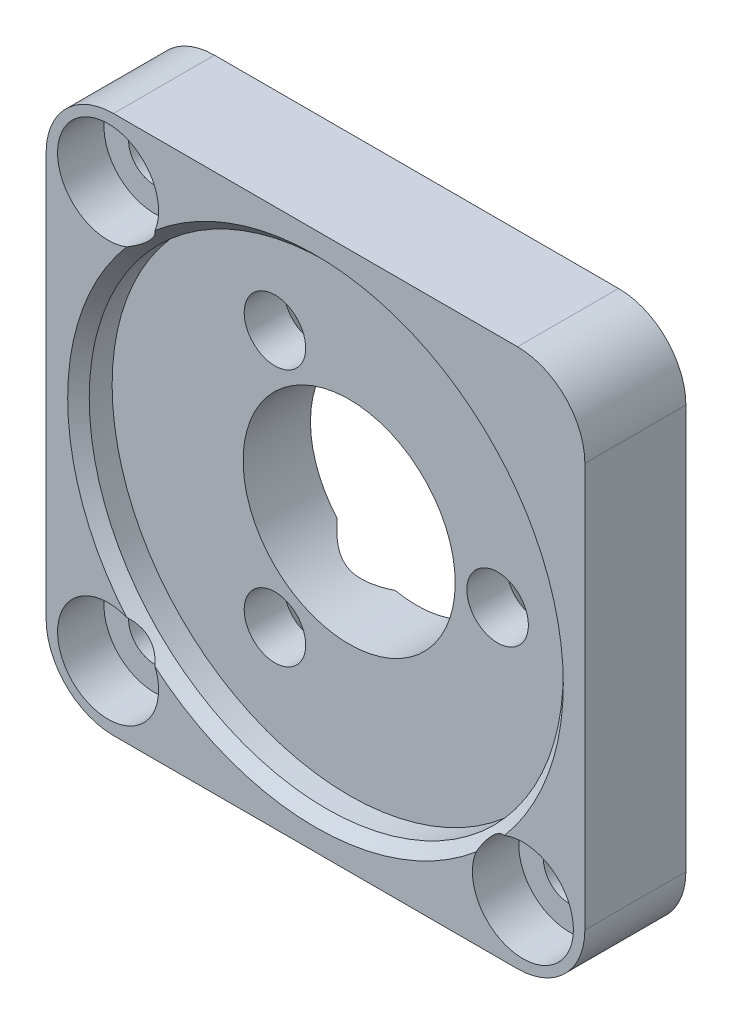
SolidWorks part; units mm, degrees
material "6063-T6"
ref_plane "Front Plane" through (0, 0, 0) normal (0, 0, 1) x (1, 0, 0)
ref_plane "Top Plane" through (0, 0, 0) normal (0, 1, 0) x (1, 0, 0)
ref_plane "Right Plane" through (0, 0, 0) normal (1, 0, 0) x (0, 0, -1)
sketch "Sketch1" plane through (0, 0, 0) normal (0, 0, 1) x (1, 0, 0)
  line L1 (-12.7, -12.7) -> (12.7, -12.7)
  line L2 (-12.7, -12.7) -> (-12.7, 12.7)
  line L3 (-12.7, 12.7) -> (12.7, 12.7)
  line L4 (12.7, -12.7) -> (12.7, 12.7)
  line L5 (-12.7, -12.7) -> (12.7, 12.7)
  line L6 (-12.7, 12.7) -> (12.7, -12.7)
  circle A0 centre (0, 0) radius 11.1125 construction
  dimension "D1" = 22.225
  dimension "D2" = 25.4
  dimension "D3" = 25.4
extrude "Boss-Extrude2" add sketch "Sketch1" along normal blind 4.7625 contours L3 L6 L5 | L6 L2 L5 | L6 L5 L1 | L5 L6 L4 region at (0, -8.4667, 0) region at (-8.4667, 0, 0) region at (8.4667, 0, 0) region at (0, 8.4667, 0)
sketch "Sketch9" plane through (0, 0, 4.7625) normal (0, 0, 1) x (1, 0, 0)
  circle A0 centre (0, 0) radius 5
  dimension "D1" = 10
extrude "Cut-Extrude1" cut sketch "Sketch9" against normal through all
hole_wizard "CSK for M2.5 Flat Head Machine Screw1" positions "Sketch6" profile "Sketch5" countersink size "M2.5" standard "Ansi Metric" end condition up to next
sketch "Sketch6" plane through (0, 0, 0) normal (0, 0, -1) x (-1, 0, 0)
  line L0 (0, 0) -> (14.8521, 0) construction
  line L2 (0, 0) -> (3.5, 6.0622) construction
  point P0 (3.5, 6.0622)
  dimension "D1" = 7
  dimension "D2" = 60
sketch "Sketch5" plane through (-3.5, 6.0622, 0) normal (1, 0, 0) x (0, 1, 0)
  line L0 (0, 0) -> (0, 4.7635)
  line L1 (0, 4.7635) -> (1.45, 4.7635)
  line L2 (1.45, 4.7635) -> (1.45, 1.3)
  line L3 (1.45, 1.3) -> (2.75, 0)
  line L5 (2.75, 0) -> (0, 0)
  line L6 (-1.45, 1.3) -> (-2.75, 0) construction
  line L11 (0, -6.35) -> (0, 107.95) construction
  dimension "Thru Hole Dia." = 2.9
  dimension "Thru Hole Depth" = 4.7635
  dimension "Near C'Sink Dia." = 5.5
  dimension "Near C'Sink Angle" = 90
hole_wizard "CBORE for #2 Socket Head Cap Screw1" positions "Sketch8" profile "Sketch7" counterbore size "#2" standard "Ansi Inch" end condition through all
sketch "Sketch8" plane through (0, 0, 4.7625) normal (0, 0, 1) x (1, 0, 0)
  line L1 (-9.779, -9.779) -> (9.779, -9.779) construction
  line L2 (-9.779, -9.779) -> (-9.779, 9.779) construction
  line L3 (-9.779, 9.779) -> (9.779, 9.779) construction
  line L4 (9.779, -9.779) -> (9.779, 9.779) construction
  line L5 (-9.779, -9.779) -> (9.779, 9.779) construction
  line L6 (-9.779, 9.779) -> (9.779, -9.779) construction
  point P5 (0, 0)
  point P238 (-9.779, -9.779)
  point P240 (9.779, -9.779)
  point P241 (-9.779, 9.779)
  dimension "D1" = 19.558
  dimension "D2" = 19.558
sketch "Sketch7" plane through (0, 0, 4.7625) normal (1, 0, 0) x (0, -1, 0)
  line L0 (0, 0) -> (0, 4.7625)
  line L1 (0, 4.7625) -> (1.2192, 4.7625)
  line L3 (1.2192, 4.7625) -> (1.2192, 2.1844)
  line L4 (1.2192, 2.1844) -> (2.3812, 2.1844)
  line L5 (2.3812, 2.1844) -> (2.3812, 0)
  line L7 (2.3812, 0) -> (0, 0)
  line L11 (0, -6.35) -> (0, 107.95) construction
  dimension "Thru Hole Dia." = 2.4384
  dimension "Thru Hole Depth" = 4.7625
  dimension "C'Bore Dia." = 4.7625
  dimension "C'Bore Depth" = 2.1844
fillet "Fillet1" radius 3.175 4 edges at (12.7, 12.7, 2.3813) (-12.7, 12.7, 2.3813) (-12.7, -12.7, 2.3813) (12.7, -12.7, 2.3813)
pattern_circular "CirPattern1" count 3 over 360 about axis through (0, 0, 0) along (0, 0, 1) of "CSK for M2.5 Flat Head Machine Screw1"
sketch "Sketch10" plane through (0, 0, 4.7625) normal (0, 0, 1) x (1, 0, 0)
  circle A0 centre (0, 0) radius 11.176
  dimension "D1" = 22.352
extrude "Cut-Extrude2" cut sketch "Sketch10" against normal blind 1.5875
chamfer "Chamfer1" distance 0.508 angle 45 1 edges at (11.176, 0, 4.7625)
